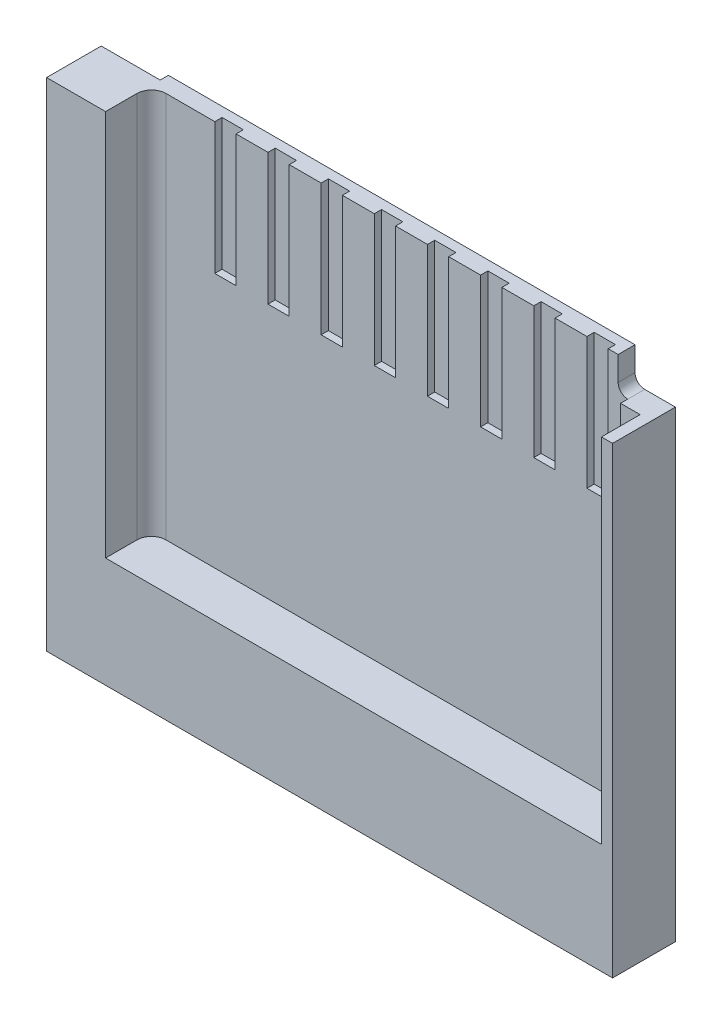
SolidWorks part; units mm, degrees
ref_plane "Płaszczyzna przednia" through (0, 0, 0) normal (0, 0, 1) x (1, 0, 0)
ref_plane "Płaszczyzna górna" through (0, 0, 0) normal (0, 1, 0) x (1, 0, 0)
ref_plane "Płaszczyzna prawa" through (0, 0, 0) normal (1, 0, 0) x (0, 0, -1)
sketch "Sketch1" plane through (0, 0, 0) normal (0, 0, 1) x (1, 0, 0)
  line L0 (4.635, 4.89) -> (5.855, 4.89) construction
  line L1 (5.855, 4.89) -> (5.855, 5.14)
  line L2 (5.855, 5.14) -> (4.635, 5.14)
  line L3 (4.635, 5.14) -> (4.635, 4.89) construction
  line L4 (3.735, -2.2544) -> (3.735, 1.69)
  line L5 (3.735, 1.69) -> (-5.205, 1.69)
  line L6 (-5.205, 1.69) -> (-5.205, -2.08)
  line L7 (-4.805, -2.48) -> (3.375, -2.48)
  line L8 (-5.205, -5.14) -> (-2.6, -5.14)
  line L9 (-2.6, -5.14) -> (-2.6, -4.06)
  line L10 (-2.6, -4.06) -> (-5.205, -4.06)
  line L11 (-5.205, -4.06) -> (-5.205, -5.14)
  line L12 (3.375, -2.48) -> (-4.805, -2.48)
  line L13 (-5.205, -2.08) -> (-5.205, -4.06)
  line L14 (-5.205, -4.06) -> (-2.6, -4.06)
  line L15 (-2.6, -4.06) -> (-2.6, -5.14)
  line L16 (-2.6, -5.14) -> (1.17, -5.14)
  line L17 (1.17, -5.14) -> (1.17, -4.06)
  line L18 (1.17, -4.06) -> (3.735, -4.06)
  line L19 (3.735, -4.06) -> (3.735, -2.2544)
  line L20 (1.17, -5.14) -> (3.735, -5.14)
  line L21 (3.735, -5.14) -> (3.735, -4.06)
  line L22 (3.735, -4.06) -> (1.17, -4.06)
  line L23 (1.17, -4.06) -> (1.17, -5.14)
  line L24 (4.845, -1.66) -> (4.845, -1.15)
  line L25 (4.845, -1.15) -> (5.855, -1.15)
  line L26 (5.855, -1.15) -> (5.855, 0.44)
  line L27 (5.855, 0.44) -> (4.865, 0.44)
  line L28 (4.865, 0.44) -> (4.865, -0.11)
  line L29 (4.865, -0.11) -> (4.455, -0.11)
  line L30 (4.455, -0.11) -> (4.455, -4.65)
  line L31 (4.455, -4.65) -> (4.685, -4.65)
  line L32 (4.685, -4.65) -> (4.845, -1.66)
  line L33 (5.19, -4.66) -> (5.855, -4.66)
  line L34 (5.855, -4.66) -> (5.855, -3.26)
  line L35 (5.855, -3.26) -> (5.19, -3.26)
  line L36 (4.94, -3.51) -> (4.94, -4.41)
  line L37 (4.685, -4.65) -> (4.455, -4.65)
  line L38 (4.455, -4.65) -> (4.455, -0.11)
  line L39 (4.455, -0.11) -> (4.865, -0.11)
  line L40 (4.865, -0.11) -> (4.865, 0.44)
  line L41 (4.865, 0.44) -> (5.855, 0.44)
  line L42 (5.855, 0.44) -> (5.855, 4.89)
  line L43 (5.855, 4.89) -> (4.635, 4.89) construction
  line L44 (4.635, 4.89) -> (4.635, 5.14) construction
  line L45 (4.635, 5.14) -> (-5.02, 5.14)
  line L46 (-5.02, 5.14) -> (-5.02, 4.64)
  line L47 (-5.22, 4.44) -> (-5.855, 4.44)
  line L48 (-5.855, 4.44) -> (-5.855, -5.14)
  line L49 (-5.855, -5.14) -> (-5.205, -5.14)
  line L50 (-5.205, -5.14) -> (-5.205, 1.69)
  line L51 (-5.205, 1.69) -> (3.735, 1.69)
  line L52 (3.735, 1.69) -> (3.735, -5.14)
  line L53 (3.735, -5.14) -> (5.855, -5.14)
  line L54 (5.855, -5.14) -> (5.855, -4.66)
  line L55 (5.855, -4.66) -> (5.19, -4.66)
  line L56 (4.94, -4.41) -> (4.94, -3.51)
  line L57 (5.19, -3.26) -> (5.855, -3.26)
  line L58 (5.855, -3.26) -> (5.855, -1.15)
  line L59 (5.855, -1.15) -> (4.845, -1.15)
  line L60 (4.845, -1.15) -> (4.845, -1.66)
  line L61 (4.845, -1.66) -> (4.685, -4.65)
  arc A0 (3.375, -2.48) -> (3.735, -2.2544) centre (3.375, -2.08) ccw
  arc A1 (-5.205, -2.08) -> (-4.805, -2.48) centre (-4.805, -2.08) ccw
  arc A2 (3.375, -2.48) -> (3.735, -2.2544) centre (3.375, -2.08) ccw
  arc A3 (-5.205, -2.08) -> (-4.805, -2.48) centre (-4.805, -2.08) ccw
  arc A4 (4.94, -4.41) -> (5.19, -4.66) centre (5.19, -4.41) ccw
  arc A5 (5.19, -3.26) -> (4.94, -3.51) centre (5.19, -3.51) ccw
  arc A6 (-5.22, 4.44) -> (-5.02, 4.64) centre (-5.22, 4.64) ccw
  arc A7 (4.94, -4.41) -> (5.19, -4.66) centre (5.19, -4.41) ccw
  arc A8 (5.19, -3.26) -> (4.94, -3.51) centre (5.19, -3.51) ccw
sketch "Sketch2" plane through (0, 0, 0) normal (0, 0, 1) x (1, 0, 0)
  line L0 (5.855, 5.14) -> (4.635, 5.14) construction
  line L1 (5.855, 4.89) -> (5.855, 5.14) construction
  line L2 (5.855, 0.44) -> (5.855, 4.89) construction
  line L3 (5.855, -1.15) -> (5.855, 0.44) construction
  line L4 (5.855, -3.26) -> (5.855, -1.15) construction
  line L5 (5.855, -4.66) -> (5.855, -3.26) construction
  line L6 (5.855, -5.14) -> (5.855, -4.66) construction
  line L7 (3.735, -5.14) -> (5.855, -5.14) construction
  line L8 (1.17, -5.14) -> (3.735, -5.14) construction
  line L9 (-2.6, -5.14) -> (1.17, -5.14) construction
  line L10 (-5.205, -5.14) -> (-2.6, -5.14) construction
  line L11 (-5.855, -5.14) -> (-5.205, -5.14) construction
  line L12 (-5.855, 4.44) -> (-5.855, -5.14) construction
  line L13 (-5.22, 4.44) -> (-5.855, 4.44) construction
  line L14 (-5.02, 5.14) -> (-5.02, 4.64) construction
  line L15 (4.635, 5.14) -> (-5.02, 5.14) construction
  line L16 (5.855, 5.14) -> (4.635, 5.14)
  line L17 (5.855, 4.89) -> (5.855, 5.14)
  line L18 (5.855, 0.44) -> (5.855, 4.89)
  line L19 (5.855, -1.15) -> (5.855, 0.44)
  line L20 (5.855, -3.26) -> (5.855, -1.15)
  line L21 (5.855, -4.66) -> (5.855, -3.26)
  line L22 (5.855, -5.14) -> (5.855, -4.66)
  line L23 (3.735, -5.14) -> (5.855, -5.14)
  line L24 (1.17, -5.14) -> (3.735, -5.14)
  line L25 (-2.6, -5.14) -> (1.17, -5.14)
  line L26 (-5.205, -5.14) -> (-2.6, -5.14)
  line L27 (-5.855, -5.14) -> (-5.205, -5.14)
  line L28 (-5.855, 4.44) -> (-5.855, -5.14)
  line L29 (-5.22, 4.44) -> (-5.855, 4.44)
  line L30 (-5.02, 5.14) -> (-5.02, 4.64)
  line L31 (4.635, 5.14) -> (-5.02, 5.14)
  arc A0 (-5.22, 4.44) -> (-5.02, 4.64) centre (-5.22, 4.64) ccw construction
  arc A1 (-5.22, 4.44) -> (-5.02, 4.64) centre (-5.22, 4.64) ccw
extrude "Boss-Extrude1" add sketch "Sketch2" along normal blind 1.3
sketch "Sketch3" plane through (0, 0, 0) normal (0, 0, -1) x (-1, 0, 0)
  line L0 (-4.635, 5.14) -> (-4.635, 4.89)
  line L1 (-4.635, 4.89) -> (-5.855, 4.89)
  line L2 (-5.855, 4.89) -> (-5.855, 5.14)
  line L3 (-5.855, 5.14) -> (-4.635, 5.14)
extrude "Cut-Extrude1" cut sketch "Sketch3" against normal blind 0.17
sketch "Sketch4" plane through (0, 0, 0) normal (0, 0, -1) x (-1, 0, 0)
  line L0 (-5.855, -3.26) -> (-5.19, -3.26) construction
  line L1 (-4.94, -3.51) -> (-4.94, -4.41) construction
  line L2 (-5.19, -4.66) -> (-5.855, -4.66) construction
  line L3 (-4.455, -4.65) -> (-4.685, -4.65) construction
  line L4 (-4.685, -4.65) -> (-4.845, -1.66) construction
  line L5 (-4.845, -1.66) -> (-4.845, -1.15) construction
  line L6 (-4.845, -1.15) -> (-5.855, -1.15) construction
  line L7 (-4.455, -0.11) -> (-4.455, -4.65) construction
  line L8 (-4.865, -0.11) -> (-4.455, -0.11) construction
  line L9 (-4.865, 0.44) -> (-4.865, -0.11) construction
  line L10 (-5.855, 0.44) -> (-4.865, 0.44) construction
  line L11 (-5.855, -3.26) -> (-5.19, -3.26)
  line L12 (-4.94, -3.51) -> (-4.94, -4.41)
  line L13 (-5.19, -4.66) -> (-5.855, -4.66)
  line L14 (-4.455, -4.65) -> (-4.685, -4.65)
  line L15 (-4.685, -4.65) -> (-4.845, -1.66)
  line L16 (-4.845, -1.66) -> (-4.845, -1.15)
  line L17 (-4.845, -1.15) -> (-5.855, -1.15)
  line L18 (-4.455, -0.11) -> (-4.455, -4.65)
  line L19 (-4.865, -0.11) -> (-4.455, -0.11)
  line L20 (-4.865, 0.44) -> (-4.865, -0.11)
  line L21 (-5.855, 0.44) -> (-4.865, 0.44)
  line L22 (-5.855, -3.26) -> (-5.855, -4.66)
  line L23 (-5.855, 0.44) -> (-5.855, -1.15)
  arc A0 (-4.94, -3.51) -> (-5.19, -3.26) centre (-5.19, -3.51) ccw construction
  arc A1 (-5.19, -4.66) -> (-4.94, -4.41) centre (-5.19, -4.41) ccw construction
  arc A2 (-4.94, -3.51) -> (-5.19, -3.26) centre (-5.19, -3.51) ccw
  arc A3 (-5.19, -4.66) -> (-4.94, -4.41) centre (-5.19, -4.41) ccw
extrude "Cut-Extrude2" cut sketch "Sketch4" against normal blind 0.17
sketch "Sketch5" plane through (0, 0, 0) normal (0, 0, -1) x (-1, 0, 0)
  line L0 (5.205, -5.14) -> (2.6, -5.14) construction
  line L1 (2.6, -5.14) -> (-1.17, -5.14) construction
  line L2 (-1.17, -5.14) -> (-3.735, -5.14) construction
  line L3 (-3.735, -5.14) -> (-3.735, -4.06) construction
  line L4 (-3.735, -4.06) -> (-3.735, -2.2544) construction
  line L5 (5.205, -4.06) -> (5.205, -5.14) construction
  line L6 (5.205, -2.08) -> (5.205, -4.06) construction
  line L7 (5.205, 1.69) -> (5.205, -2.08) construction
  line L8 (-3.735, -2.2544) -> (-3.735, 1.69) construction
  line L9 (-3.735, 1.69) -> (5.205, 1.69) construction
  line L10 (5.205, -5.14) -> (2.6, -5.14)
  line L11 (2.6, -5.14) -> (-1.17, -5.14)
  line L12 (-1.17, -5.14) -> (-3.735, -5.14)
  line L13 (-3.735, -5.14) -> (-3.735, -4.06)
  line L14 (-3.735, -4.06) -> (-3.735, -2.2544)
  line L15 (5.205, -4.06) -> (5.205, -5.14)
  line L16 (5.205, -2.08) -> (5.205, -4.06)
  line L17 (5.205, 1.69) -> (5.205, -2.08)
  line L18 (-3.735, -2.2544) -> (-3.735, 1.69)
  line L19 (-3.735, 1.69) -> (5.205, 1.69)
extrude "Cut-Extrude3" cut sketch "Sketch5" against normal blind 0.1
sketch "Sketch6" plane through (0, 0, 0.1) normal (0, 0, -1) x (-1, 0, 0)
  line L0 (-1.17, -5.14) -> (-3.735, -5.14) construction
  line L1 (-1.17, -4.06) -> (-3.735, -4.06) construction
  line L2 (-3.735, -5.14) -> (-3.735, -4.06) construction
  line L3 (-1.17, -5.14) -> (-1.17, -4.06) construction
  line L4 (2.6, -5.14) -> (2.6, -4.06) construction
  line L5 (2.6, -4.06) -> (5.205, -4.06) construction
  line L6 (5.205, -4.06) -> (5.205, -5.14) construction
  line L7 (5.205, -5.14) -> (2.6, -5.14) construction
  line L8 (5.205, 1.69) -> (5.205, -2.08) construction
  line L9 (-3.735, 1.69) -> (5.205, 1.69) construction
  line L10 (-3.735, -2.2544) -> (-3.735, 1.69) construction
  line L11 (4.805, -2.48) -> (-3.375, -2.48) construction
  line L12 (-1.17, -5.14) -> (-3.735, -5.14)
  line L13 (-1.17, -4.06) -> (-3.735, -4.06)
  line L14 (-3.735, -5.14) -> (-3.735, -4.06)
  line L15 (-1.17, -5.14) -> (-1.17, -4.06)
  line L16 (2.6, -5.14) -> (2.6, -4.06)
  line L17 (2.6, -4.06) -> (5.205, -4.06)
  line L18 (5.205, -4.06) -> (5.205, -5.14)
  line L19 (5.205, -5.14) -> (2.6, -5.14)
  line L20 (5.205, 1.69) -> (5.205, -2.08)
  line L21 (-3.735, 1.69) -> (5.205, 1.69)
  line L22 (-3.735, -2.2544) -> (-3.735, 1.69)
  line L23 (4.805, -2.48) -> (-3.375, -2.48)
  arc A0 (4.805, -2.48) -> (5.205, -2.08) centre (4.805, -2.08) ccw construction
  arc A1 (-3.735, -2.2544) -> (-3.375, -2.48) centre (-3.375, -2.08) ccw construction
  arc A2 (4.805, -2.48) -> (5.205, -2.08) centre (4.805, -2.08) ccw
  arc A3 (-3.735, -2.2544) -> (-3.375, -2.48) centre (-3.375, -2.08) ccw
extrude "Cut-Extrude4" cut sketch "Sketch6" against normal blind 0.15
mirror "Mirror1" about plane through (-5.855, 4.44, 1.3) normal (1, 0, 0) of bodies 105
delete or keep bodies "Body-Delete/Keep 1" type delete bodies bodies 105
sketch "Sketch7" plane through (0, 0, 1.3) normal (0, 0, 1) x (1, 0, 0)
  line L0 (-9.2095, 5.14) -> (-9.2095, -2.86) construction
  line L1 (-17.565, 5.14) -> (-6.69, 5.14) construction
  line L2 (-6.085, -2.86) -> (-16.345, -2.86)
  line L3 (-16.345, -2.86) -> (-16.345, 5.14)
  line L4 (-6.085, -2.86) -> (-6.085, 5.6163)
  line L5 (-6.085, 5.6163) -> (-16.345, 5.6163)
  line L6 (-16.345, 5.6163) -> (-16.345, 5.14)
  line L7 (-5.855, 4.44) -> (-5.855, -5.14) construction
  dimension "D1" = 8
  dimension "D2" = 10.26
  dimension "D3" = 0.23
extrude "Cut-Extrude5" cut sketch "Sketch7" against normal blind 0.95
sketch "Sketch8" plane through (0, 0, 0.35) normal (0, 0, 1) x (1, 0, 0)
  line L0 (-6.085, -2.86) -> (-6.085, 4.44)
  line L1 (-6.085, 4.44) -> (-6.49, 4.44)
  line L2 (-6.49, 4.44) -> (-6.49, -2.86)
  line L3 (-16.345, -2.86) -> (-6.085, -2.86) construction
  line L4 (-6.49, -2.86) -> (-6.085, -2.86)
extrude "Boss-Extrude2" add sketch "Sketch8" along normal blind 0.15
fillet "Fillet1" radius 0.3 1 edges at (-16.345, 1.14, 0.35)
sketch "Sketch9" plane through (0, 0, 0.35) normal (0, 0, 1) x (1, 0, 0)
  line L0 (-7.335, 5.14) -> (-7.335, 2.42)
  line L1 (-6.69, 5.14) -> (-16.045, 5.14) construction
  line L2 (-7.335, 2.42) -> (-6.895, 2.42)
  line L3 (-6.895, 2.42) -> (-6.895, 5.14)
  line L4 (-6.895, 5.14) -> (-7.335, 5.14)
  line L5 (-5.855, 4.44) -> (-5.855, -5.14) construction
  dimension "D1" = 1.04
  dimension "D2" = 0.44
  dimension "D3" = 2.72
extrude "Cut-Extrude6" cut sketch "Sketch9" against normal blind 0.15
pattern_linear "LPattern1" count 8 spacing 1.1 along (-1, 0, 0) of "Cut-Extrude6"
